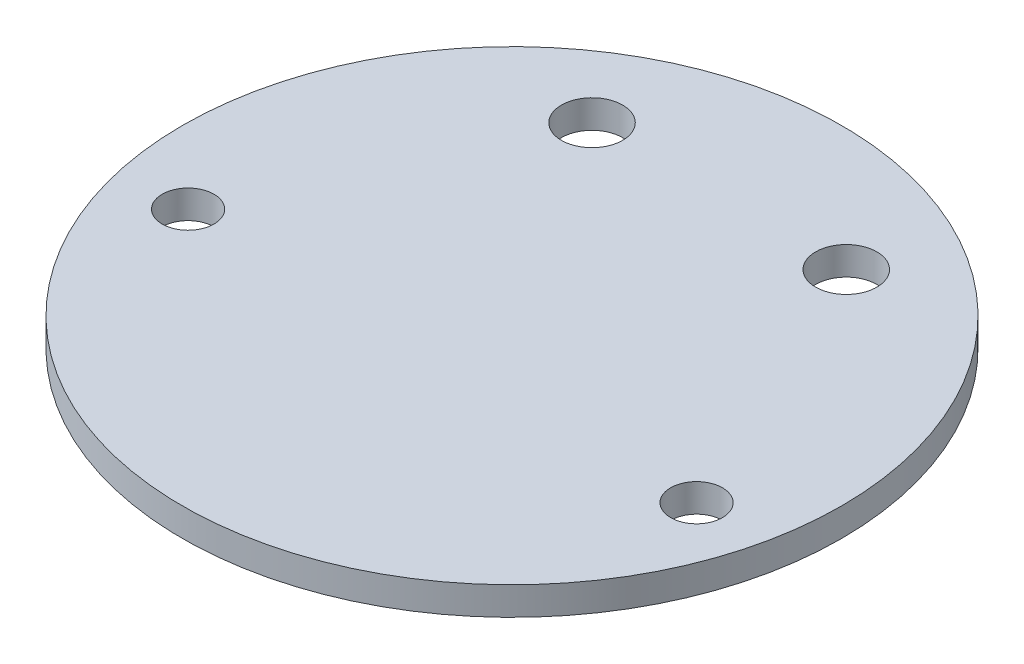
SolidWorks part; units mm, degrees
material "A-Glass Fiber"
ref_plane "Front Plane" through (0, 0, 0) normal (0, 0, 1) x (1, 0, 0)
ref_plane "Top Plane" through (0, 0, 0) normal (0, 1, 0) x (1, 0, 0)
ref_plane "Right Plane" through (0, 0, 0) normal (1, 0, 0) x (0, 0, -1)
sketch "Sketch2" plane through (0, 0, 0) normal (0, 0, 1) x (1, 0, 0)
  line L0 (0, -417.1122) -> (0, 20438.4966) construction
  line L1 (0, 0) -> (35, 0)
  line L2 (35, 0) -> (35, 3)
  line L5 (35, 3) -> (0, 3)
  line L6 (0, 3) -> (0, 0)
  dimension "D1" = 3
  dimension "D4" = 70
revolve "Revolve1" add sketch "Sketch2" angle 360 about L0
sketch "Sketch3" plane through (0, 3, 0) normal (0, 1, 0) x (1, 0, 0)
  line L0 (-13.5, 22) -> (13.5, 22) construction
  circle A0 centre (-13.5, 22) radius 3.25
  circle A1 centre (13.5, 22) radius 3.25
  point P4 (0, 22)
  dimension "D1" = 6.5
  dimension "D2" = 27
  dimension "D3" = 22
extrude "Cut-Extrude1" cut sketch "Sketch3" against normal up to next
sketch "Sketch4" plane through (0, 3, 0) normal (0, 1, 0) x (1, 0, 0)
  line L0 (-27, -7.4) -> (27, -7.4) construction
  circle A0 centre (-27, -7.4) radius 2.75
  circle A1 centre (27, -7.4) radius 2.75
  point P4 (0, -7.4)
  dimension "D3" = 5.5
  dimension "D1" = 54
  dimension "D2" = 7.4
extrude "Cut-Extrude2" cut sketch "Sketch4" against normal up to next
